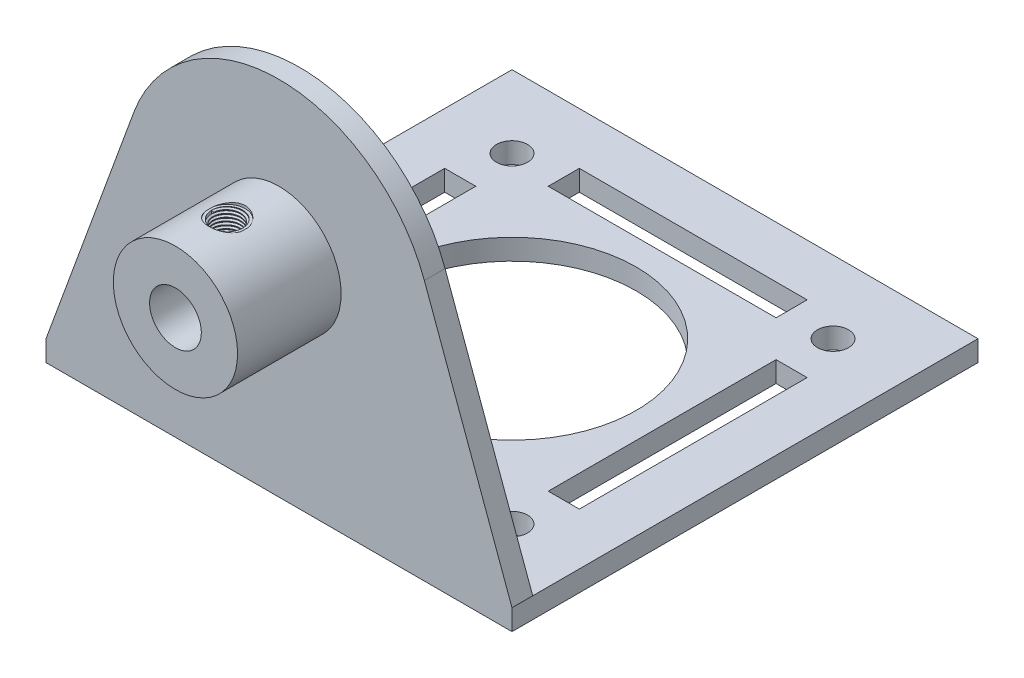
SolidWorks part; units mm, degrees
material "5052-H36"
ref_plane "前视基准面" through (0, 0, 0) normal (0, 0, 1) x (1, 0, 0)
ref_plane "上视基准面" through (0, 0, 0) normal (0, 1, 0) x (1, 0, 0)
ref_plane "右视基准面" through (0, 0, 0) normal (1, 0, 0) x (0, 0, -1)
sketch "草图1" plane through (0, 0, 0) normal (0, 1, 0) x (1, 0, 0)
  line L13 (0, 0) -> (45, 0)
  line L14 (0, 0) -> (0, 45)
  line L15 (0, 45) -> (45, 45)
  line L16 (45, 0) -> (45, 45)
extrude "凸台-拉伸1" add sketch "草图1" along normal blind 2
sketch "草图3" plane through (0, 2, 0) normal (0, 1, 0) x (1, 0, 0)
  line L0 (0, 45) -> (22.5, 45)
  line L1 (22.5, 45) -> (22.5, 22.5)
  line L3 (22.5, 22.5) -> (38, 22.5)
  line L4 (38, 22.5) -> (38, 38)
  line L5 (38, 38) -> (7, 38)
  line L6 (7, 38) -> (7, 7)
  line L7 (7, 7) -> (38, 7)
  circle A0 centre (22.5, 22.5) radius 12
  circle A1 centre (38, 38) radius 1.5
  circle A2 centre (7, 38) radius 1.5
  circle A3 centre (7, 7) radius 1.5
  circle A4 centre (38, 7) radius 1.5
extrude "切除-拉伸1" cut sketch "草图3" against normal blind 10 contours A2 | A1 | A4 | A3 | A0
sketch "草图7" plane through (0, 2, 0) normal (0, 1, 0) x (1, 0, 0)
  line L0 (0, 0) -> (0, 2)
  line L1 (0, 0) -> (0, 45) construction
  line L2 (0, 2) -> (45, 2)
  line L3 (45, 0) -> (45, 45) construction
  line L4 (45, 2) -> (45, 0)
  line L5 (45, 0) -> (0, 0)
extrude "凸台-拉伸3" add sketch "草图7" along normal blind 40
sketch "草图8" plane through (0, 0, 0) normal (0, 0, 1) x (1, 0, 0)
  line L0 (22.5, 0) -> (22.5, 20)
  line L1 (0, 0) -> (45, 0) construction
  circle A0 centre (22.5, 20) radius 2.5
  circle A1 centre (22.5, 20) radius 6
extrude "凸台-拉伸4" add sketch "草图8" along normal blind 10
sketch "草图10" plane through (0, 0, 0) normal (0, 0, 1) x (1, 0, 0)
  line L0 (0, 0) -> (0, 2)
  line L1 (0, 42) -> (0, 0) construction
  line L2 (0, 2) -> (8.463, 25.1349)
  line L3 (45, 0) -> (45, 2)
  line L4 (45, 42) -> (45, 0) construction
  line L5 (45, 2) -> (36.537, 25.1349)
  line L6 (0, 2) -> (0, 42)
  line L7 (0, 42) -> (45, 42)
  line L8 (45, 42) -> (45, 2)
  circle A0 centre (22.5, 20) radius 14.9467
  line M4 (45, 0) -> (45, 42)
  line M5 (45, 42) -> (0, 42)
  line M6 (0, 42) -> (0, 0)
extrude "切除-拉伸3" cut sketch "草图10" against normal blind 10 contours A0 L5 L2 M4 M5 M6
sketch "草图12" plane through (0, 2, 0) normal (0, 1, 0) x (1, 0, 0)
  line L0 (7, 38) -> (7, 7)
  line L1 (7, 22.5) -> (8, 22.5)
  line L2 (7, 22.5) -> (5, 22.5)
  line L3 (5, 22.5) -> (5, 33.5)
  line L4 (5, 33.5) -> (8, 33.5)
  line L5 (8, 33.5) -> (8, 11.5)
  line L6 (5, 22.5) -> (5, 11.5)
  line L7 (5, 11.5) -> (8, 11.5)
  line L8 (7, 7) -> (38, 7)
  line L9 (22.5, 7) -> (22.5, 8)
  line L10 (22.5, 7) -> (22.5, 5)
  line L11 (22.5, 8) -> (11.5, 8)
  line L12 (11.5, 8) -> (11.5, 5)
  line L13 (11.5, 5) -> (33.5, 5)
  line L14 (33.5, 5) -> (33.5, 8)
  line L15 (22.5, 8) -> (33.5, 8)
  line L16 (38, 7) -> (38, 38)
  line L17 (38, 38) -> (7, 38)
  line L18 (38, 22.5) -> (37, 22.5)
  line L19 (37, 22.5) -> (37, 11.5)
  line L20 (37, 11.5) -> (40, 11.5)
  line L21 (40, 11.5) -> (40, 33.5)
  line L22 (40, 33.5) -> (37, 33.5)
  line L23 (37, 33.5) -> (37, 22.5)
  line L24 (22.5, 38) -> (22.5, 40)
  line L25 (22.5, 40) -> (11.5, 40)
  line L26 (11.5, 40) -> (11.5, 37)
  line L27 (11.5, 37) -> (33.5, 37)
  line L28 (33.5, 37) -> (33.5, 40)
  line L29 (33.5, 40) -> (22.5, 40)
extrude "切除-拉伸4" cut sketch "草图12" against normal blind 10 contours L3 L4 L5 L7 L6 | L25 L26 L27 L28 L29 | L19 L20 L21 L22 L23 | L11 L12 L13 L14 L15
sketch "草图15" plane through (0, 0, 0) normal (0, 0, 1) x (1, 0, 0)
  line L0 (22.5, 0) -> (22.5, 20)
  line L1 (0, 0) -> (45, 0) construction
ref_plane "基准面2" through (22.5, 20, 0) normal (0, 1, 0) x (1, 0, 0)
sketch "草图16" plane through (22.5, 20, 0) normal (0, 1, 0) x (1, 0, 0)
  line L0 (0, 0) -> (0, -5)
  line L1 (-6, 0) -> (6, 0) construction
  circle A0 centre (0, -5) radius 1.75
extrude "切除-拉伸5" cut sketch "草图16" against normal mid plane 5
sketch "草图17" plane through (22.5, 20, 0) normal (0, 1, 0) x (1, 0, 0)
  line L0 (0, 0) -> (0, -5)
  line L1 (-6, 0) -> (6, 0) construction
  circle A0 centre (0, -5) radius 1.5
extrude "切除-拉伸6" cut sketch "草图17" against normal mid plane 11.5
sketch "草图18" plane through (0, 14.25, 0) normal (0, 1, 0) x (1, 0, 0)
  line L0 (22.5, 0) -> (22.5, -5)
  line L1 (8.463, 0) -> (36.537, 0) construction
  circle A0 centre (22.5, -5) radius 1.75
extrude "切除-拉伸8" cut sketch "草图18" against normal blind 11.5 contours A0
sketch "草图19" plane through (0, 25.75, 0) normal (0, -1, 0) x (1, 0, 0)
  circle A0 centre (22.5, 5) radius 1.75
extrude "切除-拉伸9" cut sketch "草图19" against normal blind 11.5
thread "螺纹线1" pitch 0.3175 start angle 0, offset 0, length 3, pitch 0.3175, diameter 3
ref_plane "基准面3" through (24, 14.25, 5) normal (0, 0, 1) x (1, 0, 0)
sketch "螺纹线轮廓1" plane through (24, 14.25, 5) normal (0, 0, 1) x (1, 0, 0)
  line L0 (0, 0) -> (0, 0.3175) construction
  line L11 (0, 0) -> (0, 0.2778)
  line L12 (0, 0.2778) -> (-0.1719, 0.1786)
  line L13 (-0.1719, 0.1786) -> (-0.1719, 0.0992)
  line L15 (-0.1719, 0.0992) -> (0, 0)
  line L17 (-0.1719, 0.1389) -> (0, 0.1389) construction
  point P2 (0, 0)
  dimension "Pitch" = 0.3175
  dimension "Profile_Angle" = 60
  dimension "Profile_Land" = 0.0794
  dimension "Profile_Height" = 0.1719
thread "螺纹线2" pitch 0.3175 profile "螺纹线轮廓2" start angle 0, offset 0, length 3, pitch 0.3175, diameter 3
ref_plane "基准面4" through (21, 25.75, 5) normal (0, 0, 1) x (-1, 0, 0)
sketch "螺纹线轮廓2" plane through (21, 25.75, 5) normal (0, 0, 1) x (-1, 0, 0)
  line L0 (0, 0) -> (0, 0.3175) construction
  line L11 (0, 0) -> (0, 0.2778)
  line L12 (0, 0.2778) -> (-0.1719, 0.1786)
  line L13 (-0.1719, 0.1786) -> (-0.1719, 0.0992)
  line L15 (-0.1719, 0.0992) -> (0, 0)
  line L17 (-0.1719, 0.1389) -> (0, 0.1389) construction
  point P2 (0, 0)
  dimension "Pitch" = 0.3175
  dimension "Profile_Angle" = 60
  dimension "Profile_Land" = 0.0794
  dimension "Profile_Height" = 0.1719
